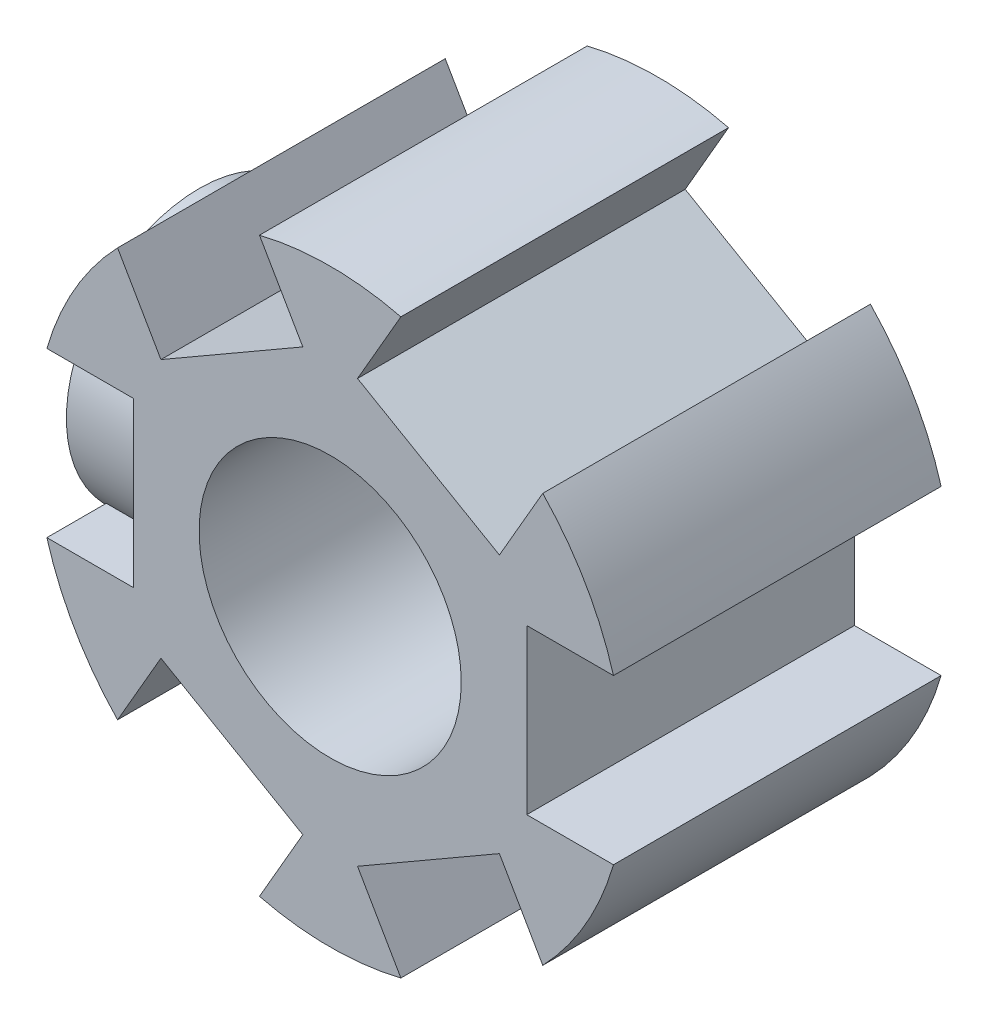
SolidWorks part; units mm, degrees
ref_plane "Top Plane" through (0, 0, 0) normal (0, 0, 1) x (1, 0, 0)
ref_plane "Right Plane" through (0, 0, 0) normal (0, 1, 0) x (1, 0, 0)
ref_plane "Front Plane" through (0, 0, 0) normal (1, 0, 0) x (0, 0, -1)
ref_axis "x-axis" through (-88.99, 0, 0) along (1, 0, 0)
ref_axis "y-axis" through (0, -55, 0) along (0, 1, 0)
ref_axis "z-axis" through (0, 0, 55) along (0, 0, -1)
sketch "Sketch1" plane through (0, 0, 0) normal (0, 0, 1) x (1, 0, 0)
  line L8 (-19.9785, 0) -> (0, 0) construction
  line L16 (0, 0) -> (0, -20.7846) construction
  line L23 (0, 0) -> (0, -20.7846) construction
  circle A0 centre (0, 0) radius 4
  circle A3 centre (0, 0) radius 9
  dimension "D1" = 8
  dimension "D2" = 18
extrude "Boss-Extrude1" add sketch "Sketch1" along normal mid plane 10
ref_plane "Plane1" through (-9, 0, 0) normal (-1, 0, 0) x (0, 0, 1)
sketch "Sketch2" plane through (-9, -17.1931, 0) normal (1, 0, 0) x (0, -1, 0)
  line L1 (-19.6931, -5) -> (-14.6931, -5)
  line L2 (-19.6931, -5) -> (-19.6931, 5)
  line L3 (-19.6931, 5) -> (-14.6931, 5)
  line L4 (-14.6931, -5) -> (-14.6931, 5)
  line L5 (-19.6931, -5) -> (-14.6931, 5) construction
  line L6 (-19.6931, 5) -> (-14.6931, -5) construction
  dimension "D2" = 10
  dimension "D3" = 5
extrude "Cut-Extrude3" cut sketch "Sketch2" along normal blind 3
pattern_circular "CirPattern1" count 6 over 360 about axis through (0, 0, 5) along (0, 0, 1) of "Cut-Extrude3"
sketch "Sketch3" plane through (-6, 0, 0) normal (-1, 0, 0) x (0, -1, 0)
  circle A0 centre (0, 0) radius 4.05
  dimension "D1" = 4.05
extrude "Boss-Extrude2" add sketch "Sketch3" along normal blind 3
